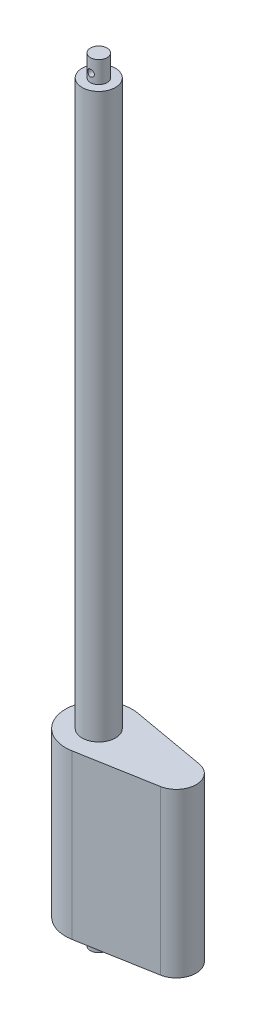
SolidWorks part; units mm, degrees
ref_plane "Front" through (0, 0, 0) normal (0, 0, 1) x (1, 0, 0)
ref_plane "Top" through (0, 0, 0) normal (0, 1, 0) x (1, 0, 0)
ref_plane "Right" through (0, 0, 0) normal (1, 0, 0) x (0, 0, -1)
sketch "Sketch7" plane through (0, 0, 0) normal (1, 0, 0) x (0, 0, -1)
  line L1 (-20, 7) -> (-20, 105)
  line L4 (-10, 443) -> (-5, 443)
  line L5 (-5, 443) -> (-5, 456)
  line L6 (-5, 456) -> (0, 456)
  line L7 (0, 456) -> (0, -8)
  line L9 (-5, -8) -> (0, -8)
  line L10 (-10, 443) -> (-10, 105)
  line L11 (-10, 105) -> (-20, 105)
  line L12 (-5, -8) -> (-5, 7)
  line L13 (-5, 7) -> (-20, 7)
  point P11 (0, 0)
  point P12 (0, 448)
  point P13 (0, 455)
  dimension "D1" = 8
  dimension "D2" = 8
  dimension "D3" = 98
  dimension "D5" = 12
  dimension "D7" = 10
  dimension "D8" = 20
  dimension "D11" = 5
  dimension "D9" = 15
  dimension "D10" = 5
  dimension "D4" = 1
  dimension "D6" = 455
revolve "Revolve2" add sketch "Sketch7" angle 360 about L7
sketch "Sketch8" plane through (0, 0, 0) normal (0, 0, 1) x (1, 0, 0)
  line L0 (-5, -8) -> (5, -8) construction
  line L2 (0, 456) -> (0, 448) construction
  line L3 (5, 456) -> (-5, 456) construction
  line L4 (-5, -8) -> (5, -8) construction
  line L5 (0, -8) -> (0, 0) construction
  circle A1 centre (0, 448) radius 2
  circle A2 centre (0, 0) radius 2
  dimension "D2" = 8
  dimension "D1" = 4
  dimension "D4" = 4
  dimension "D3" = 8
extrude "Cut-Extrude2" cut sketch "Sketch8" against normal through all and the other way through all
sketch "Sketch10" plane through (0, 105, 0) normal (0, 1, 0) x (1, 0, 0)
  line L0 (0, 0) -> (46.5567, 0) construction
  line L1 (3.491, 19.693) -> (48.6292, 11.6912)
  line L2 (48.6292, -11.6912) -> (3.491, -19.693)
  circle A1 centre (0, 0) radius 20 construction
  arc A2 (48.6292, 11.6912) -> (48.6292, -11.6912) centre (46.5567, 0) cw
  arc A3 (3.491, 19.693) -> (3.491, -19.693) centre (0, 0) ccw
extrude "Boss-Extrude4" add sketch "Sketch10" against normal up to surface (98 mm away) up to face at (0, 7, 5)
sketch "Sketch11" plane through (0, 0, 0) normal (0, 0, 1) x (1, 0, 0)
  line L0 (0, 448) -> (0, 0)
equation "\"mountingHoleDistance\"=8"
equation "\"actuatorLength\"= 1"
equation "\"D1@Sketch7\"= \"mountingHoleDistance\""
equation "\"D2@Sketch7\"=\"mountingHoleDistance\""
equation "\"MotorHousingHeight\"= 98"
equation "\"D3@Sketch7\"=\"MotorHousingHeight\""
equation "\"acutatorMinimumLength\" = 455"
equation "\"D3@Sketch8\"=\"mountingHoleDistance\""
equation "\"D2@Sketch8\"=\"mountingHoleDistance\""
equation "\"D4@Sketch7\"=\"actuatorLength\""
equation "\"D6@Sketch7\"=\"acutatorMinimumLength\""
